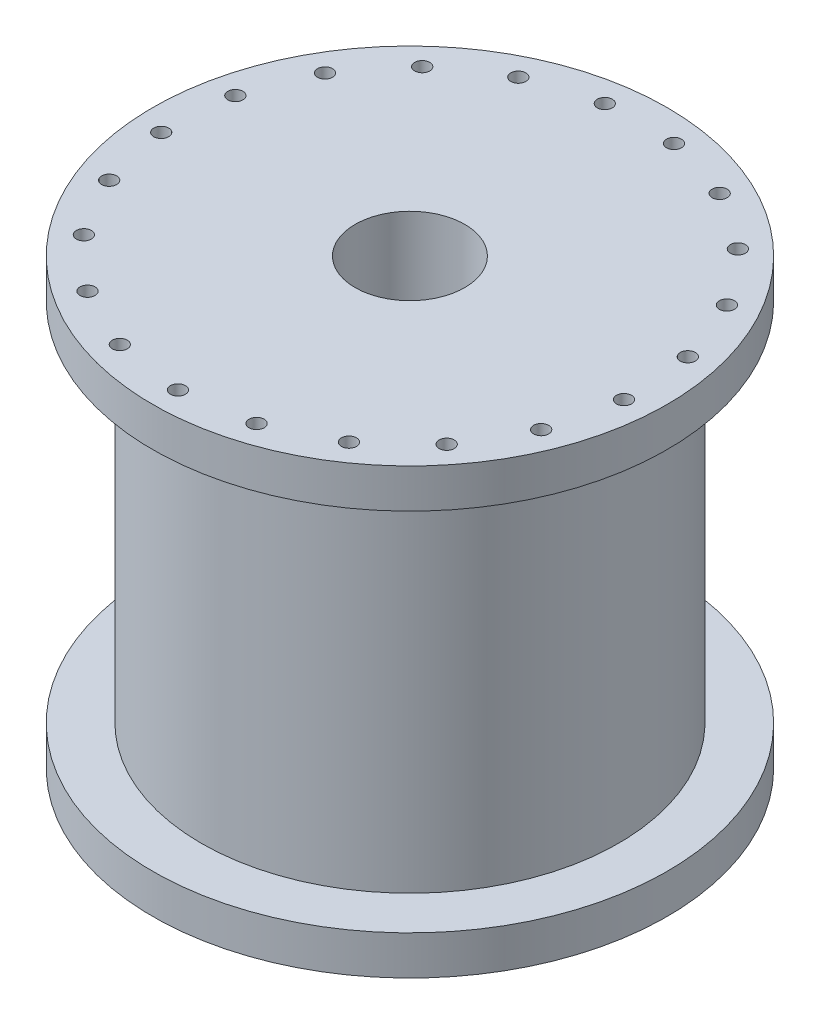
SolidWorks part; units mm, degrees
ref_plane "Front Plane" through (0, 0, 0) normal (0, 0, 1) x (1, 0, 0)
ref_plane "Top Plane" through (0, 0, 0) normal (0, 1, 0) x (1, 0, 0)
ref_plane "Right Plane" through (0, 0, 0) normal (1, 0, 0) x (0, 0, -1)
sketch "Sketch3" plane through (0, 0, 0) normal (1, 0, 0) x (0, 0, -1)
  line L0 (0, 0) -> (0, 45.4794)
  line L1 (0, 45.4794) -> (26.3744, 45.4794)
  line L2 (26.3744, 45.4794) -> (26.3744, 41.4666)
  line L3 (26.3744, 41.4666) -> (21.3957, 41.4666)
  line L4 (21.3957, 41.4666) -> (21.3957, 4.0129)
  line L5 (21.3957, 4.0129) -> (26.3744, 4.0129)
  line L6 (26.3744, 4.0129) -> (26.3744, 0)
  line L7 (26.3744, 0) -> (0, 0)
  line L8 (0, 0) -> (0.0836, -0.1672)
  line L9 (0, 45.4794) -> (0, 51.4239) construction
revolve "Revolve1" add sketch "Sketch3" angle 360 about L9 region at (0, 22.7397, -11.218)
sketch "Sketch4" plane through (0, 45.4794, 0) normal (0, 1, 0) x (1, 0, 0)
  circle A0 centre (0, 0) radius 5.6215
extrude "Cut-Extrude1" cut sketch "Sketch4" against normal through all
sketch "Sketch5" plane through (0, 41.4666, 0) normal (0, -1, 0) x (1, 0, 0)
  line L0 (0, 0) -> (0, 27.7041) construction
  circle A0 centre (0, 23.7951) radius 0.7712
  dimension "D1" = 1.5423
extrude "Cut-Extrude2" cut sketch "Sketch5" against normal through all
pattern_circular "CirPattern2" count 21 over 360 about axis through (0, 0, 0) along (0, 1, 0) of "Cut-Extrude2"
sketch "Sketch7" plane through (0, 0, 0) normal (0, -1, 0) x (1, 0, 0)
  line L0 (0, 0) -> (-4.431, 25.9996) construction
  circle A0 centre (0, 0) radius 26.3744 construction
  circle A1 centre (0, 0) radius 26.3744 construction
  circle A2 centre (-3.992, 23.4238) radius 0.762
  point P9 (18.2157, 24.6326)
  dimension "D1" = 1.524
equation "\"Spoke hole diameter\"= \"D1@Sketch5\""
